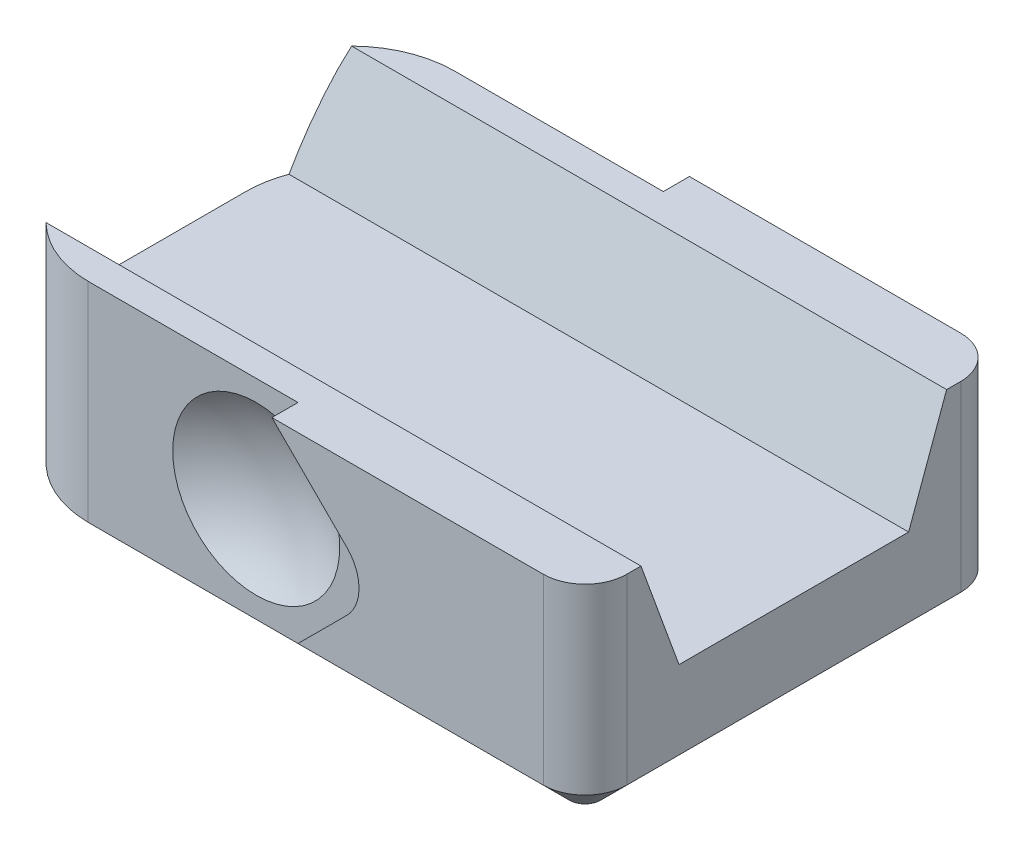
SolidWorks part; units mm, degrees
ref_plane "Front Plane" through (0, 0, 0) normal (0, 0, 1) x (1, 0, 0)
ref_plane "Top Plane" through (0, 0, 0) normal (0, 1, 0) x (1, 0, 0)
ref_plane "Right Plane" through (0, 0, 0) normal (1, 0, 0) x (0, 0, -1)
sketch "Sketch1" plane through (0, 0, 0) normal (0, 1, 0) x (1, 0, 0)
  line L1 (-11.1892, -12.7) -> (16.51, -12.7)
  line L2 (-19.05, -4.7625) -> (-19.05, 4.7625)
  line L3 (-11.1892, 12.7) -> (16.51, 12.7)
  line L4 (19.05, -10.16) -> (19.05, 10.16)
  line L5 (-19.05, -12.7) -> (19.05, 12.7) construction
  line L6 (-19.05, 12.7) -> (19.05, -12.7) construction
  line L10 (-19.05, 0) -> (19.05, 0) construction
  line L11 (-12.7771, 11.112) -> (-11.1892, 12.7)
  line L12 (-12.7771, -11.112) -> (-11.1892, -12.7)
  arc A2 (16.51, -12.7) -> (19.05, -10.16) centre (16.51, -10.16) ccw
  arc A3 (16.51, 12.7) -> (19.05, 10.16) centre (16.51, 10.16) cw
  arc A4 (-19.05, 4.7625) -> (-12.7771, 11.112) centre (-12.7, 4.7625) cw
  arc A5 (-19.05, -4.7625) -> (-12.7771, -11.112) centre (-12.7, -4.7625) ccw
  point P0 (0, 0)
  dimension "D3" = 4.7625
  dimension "D4" = 2.54
  dimension "D5" = 6.35
  dimension "D1" = 25.4
  dimension "D2" = 38.1
  dimension "D6" = 45
  dimension "D7" = 1.588
extrude "Boss-Extrude1" add sketch "Sketch1" along normal blind 12.7
sketch "Sketch2" plane through (-19.05, 0, 0) normal (-1, 0, 0) x (0, 0, 1)
  line L0 (-12.7, 6.35) -> (12.7, 6.35) construction
  line L3 (0, 12.7) -> (0, 0) construction
  line L5 (-9.525, 6.35) -> (-9.525, 12.7)
  line L12 (-9.525, 6.35) -> (9.525, 6.35)
  line L13 (-12.7, 12.7) -> (-12.7, 0) construction
  line L14 (11.112, 12.7) -> (4.7625, 12.7) construction
  line L15 (-9.525, 12.7) -> (9.525, 12.7)
  line L17 (9.525, 12.7) -> (9.525, 6.35)
  line L18 (12.7, 12.7) -> (12.7, 0) construction
  point P0 (0, 0)
  point P16 (0, 6.35)
  dimension "D2" = 19.05
  dimension "D1" = 19.05
extrude "Cut-Extrude1" cut sketch "Sketch2" against normal through all
chamfer "Chamfer1" distance 2.54 angle 70 2 edges at (1.0749, 6.35, 9.525) (1.0749, 6.35, -9.525)
sketch "Sketch4" plane through (0, 0, 12.7) normal (0, 0, 1) x (1, 0, 0)
  line L1 (-19.05, 0) -> (0, 0)
  line L9 (-19.05, 0) -> (-19.05, 12.7)
  line L11 (-19.05, 12.7) -> (0, 12.7)
  line L13 (-19.05, 6.35) -> (6.35, 6.35) construction
  line L14 (0, 12.7) -> (4.5539, 8.1461)
  line L15 (4.5539, 4.5539) -> (0, 0)
  line L16 (-11.1892, 12.7) -> (16.51, 12.7) construction
  arc A1 (4.5539, 4.5539) -> (4.5539, 8.1461) centre (2.7579, 6.35) ccw
  dimension "D4" = 2.54
  dimension "D1" = 25.4
  dimension "D2" = 45
  dimension "D3" = 45
extrude "Cut-Extrude3" cut sketch "Sketch4" against normal blind 1.5875
ref_plane "Plane1" through (-2.54, 0, 0) normal (-1, 0, 0) x (0, 0, 1)
sketch "Sketch6" plane through (-2.54, 0, 0) normal (-1, 0, 0) x (0, 0, 1)
  line L0 (0, 6.35) -> (11.1125, 6.35) construction
  line L2 (11.1125, 6.35) -> (11.1125, 11.43)
  line L4 (11.1125, 6.35) -> (9.525, 6.35)
  line L5 (-4.7625, 6.35) -> (4.7625, 6.35) construction
  arc A0 (11.1125, 11.43) -> (9.525, 6.35) centre (18.4467, 6.35) ccw
  point P1 (0, 0)
  dimension "D3" = 8.9217
  dimension "D1" = 5.08
  dimension "D2" = 1.5875
  dimension "D4" = 11.1125
revolve "Cut-Revolve1" cut sketch "Sketch6" angle 360 about L0
ref_plane "Plane2" through (0, 0, 0) normal (0, 0, -1) x (-1, 0, 0)
mirror "Mirror1" about plane through (0, 0, 0) normal (0, 0, -1) of "Cut-Extrude3", "Cut-Revolve1"
chamfer "Chamfer3" distance 1.5875 angle 45 5 edges at (8.255, 0, 12.7) (18.3061, 0, 11.9561) (19.05, 0, 0) (18.3061, 0, -11.9561) (8.255, 0, -12.7)
